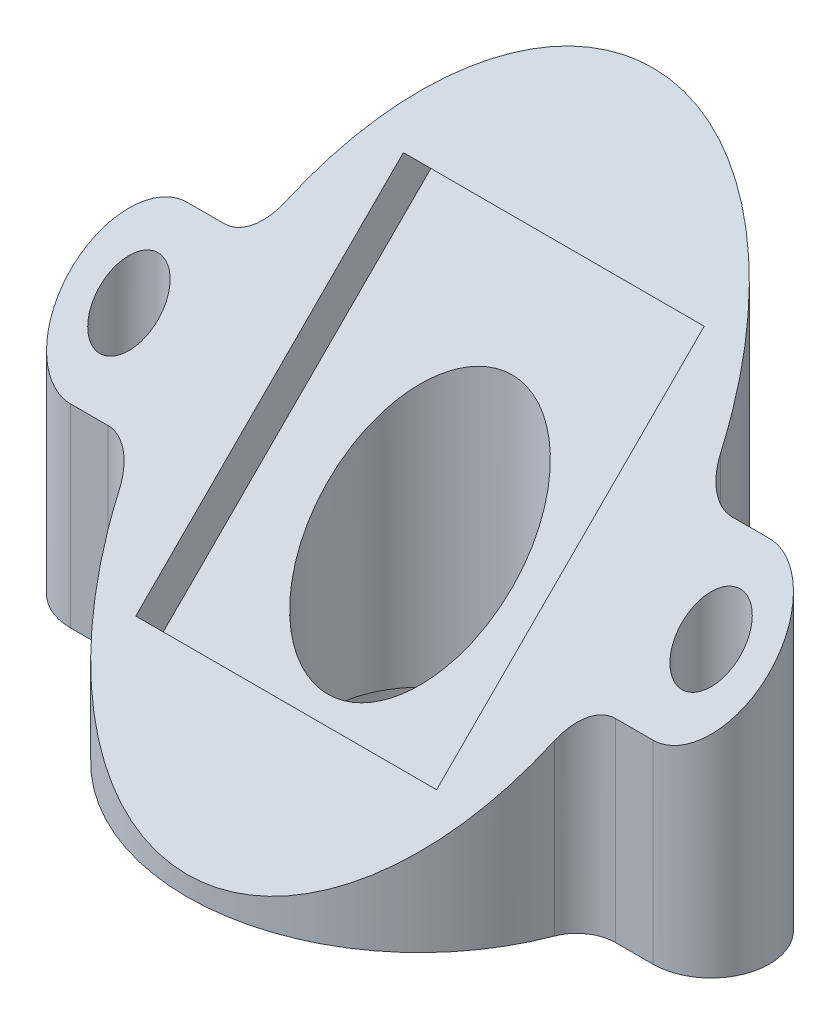
SolidWorks part; units mm, degrees
ref_plane "Front Plane" through (0, 0, 0) normal (0, 0, 1) x (1, 0, 0)
ref_plane "Top Plane" through (0, 0, 0) normal (0, 1, 0) x (1, 0, 0)
ref_plane "Right Plane" through (0, 0, 0) normal (1, 0, 0) x (0, 0, -1)
sketch "Sketch2" plane through (0, 0, 0) normal (0, 1, 0) x (1, 0, 0)
  circle A0 centre (0, 0) radius 4.75
  circle A1 centre (0, 0) radius 6.5
  circle A2 centre (0, 0) radius 12
  circle A3 centre (0, 0) radius 7.5
extrude "Boss-Extrude2" add sketch "Sketch2" against normal blind 1 contours A1 A0 | A3 A1 | A2 A3 region at (-6.3162, 0, 0) region at (-11.6606, 0, 0) region at (-7.2879, 0, 0)
extrude "Boss-Extrude3" add sketch "Sketch2<4>" against normal blind 3 contours A3 A1 region at (-7.2879, 0, 0)
sketch "Sketch2<4>" plane through (0, 0, 0) normal (0, 1, 0) x (1, 0, 0) same geometry as "Sketch2"
extrude "Boss-Extrude4" add sketch "Sketch2<5>" along normal blind 24 contours A0 | A2 region at (0, 0, 0)
sketch "Sketch2<5>" plane through (0, 0, 0) normal (0, 1, 0) x (1, 0, 0) same geometry as "Sketch2"
sketch "Sketch5" plane through (0, 0, 0) normal (1, 0, 0) x (0, 0, -1)
  line L0 (-12, -1) -> (-12, 0)
  line L1 (-12, 24) -> (-12, -1) construction
  line L2 (-12, 0) -> (12, 24)
  line L3 (12, 24) -> (12, -1)
  line L4 (12, -1) -> (-12, -1)
  line L5 (-12, 0) -> (-12, 24)
  line L6 (-12, 24) -> (12, 24)
  line L7 (-12, 24) -> (-12, 0)
extrude "Cut-Extrude1" cut sketch "Sketch5" against normal through all both and the other way through all contours L6 L5 L2 region at (0, 16, 4)
sketch "Sketch10" plane through (0, 6, 6) normal (0, 0.7071, 0.7071) x (1, 0, 0)
  line L0 (-12, 8.4853) -> (12, 8.4853)
  line L2 (-7.75, -1.2647) -> (7.75, -1.2647)
  line L3 (-7.75, -1.2647) -> (-7.75, 18.2353)
  line L4 (-7.75, 18.2353) -> (7.75, 18.2353)
  line L5 (7.75, -1.2647) -> (7.75, 18.2353)
  line L6 (-7.75, -1.2647) -> (7.75, 18.2353) construction
  line L7 (-7.75, 18.2353) -> (7.75, -1.2647) construction
  point P4 (0, 8.4853)
  ellipse M4 centre (0, 8.4853) end of major axis (0, 15.2028) minor radius 4.75
  dimension "D1" = 15.5
  dimension "D2" = 19.5
extrude "Cut-Extrude5" cut sketch "Sketch10" against normal blind 2 contours L2 L5 L0 L3 M4 | L0 L5 L4 L3 M4 region at (-7.5669, 15.4471, -3.4471) region at (-6.25, 11.8705, 0.1295)
sketch "Sketch11" plane through (0, -0.8943, 0.8943) normal (0, 0.7071, -0.7071) x (-1, 0, 0)
  line L0 (7.75, 6.4853) -> (-7.75, 6.4853) construction
  line L1 (-7.75, 8.4853) -> (7.75, 8.4853)
  line L2 (-7.75, 8.4853) -> (-7.75, 6.4853)
  line L3 (-7.75, 6.4853) -> (7.75, 6.4853)
  line L4 (7.75, 8.4853) -> (7.75, 6.4853)
extrude "Cut-Extrude6" cut sketch "Sketch11" along normal blind 18
thread "Thread2" pitch 1 method extrude profile "Thread Profile2" start angle 0, offset 0, length 0, pitch 1, diameter 15
ref_plane "Plane2" through (7.5, -3, 0) normal (0, 0, 1) x (1, 0, 0)
sketch "Thread Profile2" plane through (7.5, -3, 0) normal (0, 0, 1) x (1, 0, 0)
  line L0 (0, 0) -> (0, 1) construction
  line L1 (0, 0) -> (0.5413, 0.3125)
  line L2 (0.5413, 0.3125) -> (0.5413, 0.4375)
  line L3 (0.5413, 0.4375) -> (0, 0.75)
  line L4 (0.5413, 0.375) -> (0, 0.375) construction
  line L11 (0, 0) -> (0, 0.75)
  point P2 (0, 0)
  dimension "Pitch" = 1
  dimension "Profile_Angle" = 60
  dimension "Profile_Land" = 0.125
  dimension "Profile_Height" = 0.5413
sketch "Sketch15" plane through (0, -1, 0) normal (0, -1, 0) x (1, 0, 0)
  line L0 (0, 0) -> (15, 0)
  line L1 (15, 3) -> (11.619, 3)
  line L2 (15, -3) -> (11.619, -3)
  line L3 (0, 0) -> (0, -4.1517)
  line L4 (0, -13.2) -> (0, 13.2) construction
  line L5 (-15, -3) -> (-11.619, -3)
  line L6 (-15, 3) -> (-11.619, 3)
  circle A0 centre (0, 0) radius 12
  circle A1 centre (15, 0) radius 3
  circle A2 centre (15, 0) radius 1.5
  circle A3 centre (-15, 0) radius 1.5
  circle A4 centre (-15, 0) radius 3
  circle M7 centre (0, 0) radius 12
extrude "Boss-Extrude5" add sketch "Sketch15" against normal up to surface (16 mm away) contours A2 A1 | A1 L2 M7 | A1 L1 M7 | A4 A3 | A0 A4 L5 | L6 A4 M7 region at (12.5416, -1, -2.3172) region at (12.5416, -1, 2.3172) region at (12.9387, -1, 2.0613) region at (-12.5416, -1, 2.3172) region at (-12.5416, -1, -2.3172) region at (-12.9387, -1, 2.0613) up to face at (0, 12, 0)
fillet "Fillet1" radius 2 4 edges at (11.619, 7, -3) (11.619, 4, 3) (-11.619, 7, -3) (-11.619, 4, 3)
